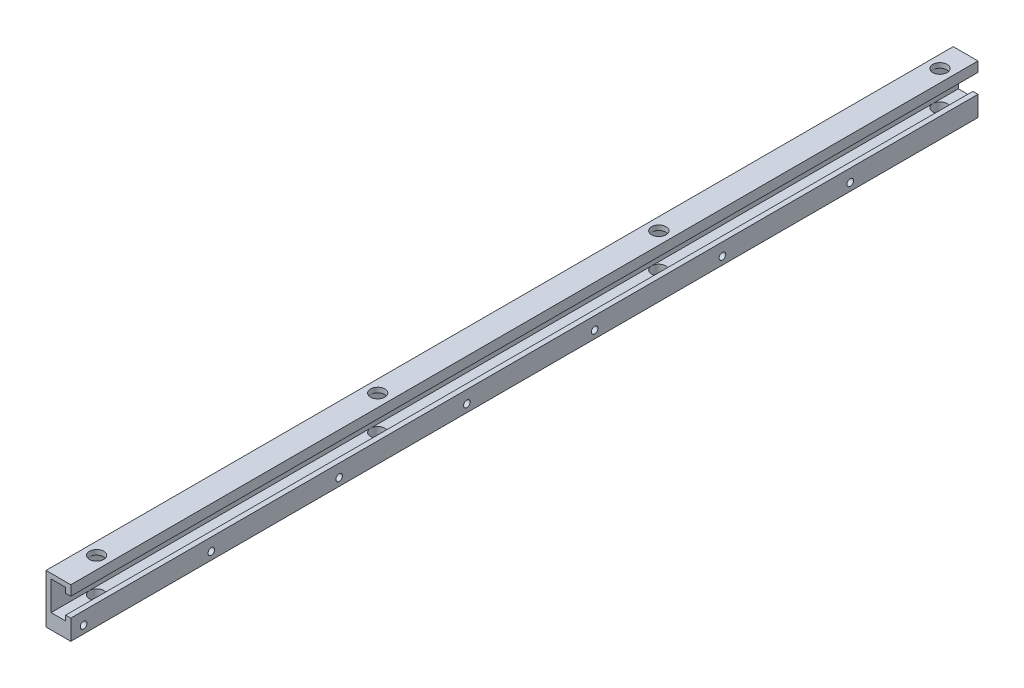
SolidWorks part; units mm, degrees
ref_plane "前视基准面" through (0, 0, 0) normal (0, 0, 1) x (1, 0, 0)
ref_plane "上视基准面" through (0, 0, 0) normal (0, 1, 0) x (1, 0, 0)
ref_plane "右视基准面" through (0, 0, 0) normal (1, 0, 0) x (0, 0, -1)
sketch "草图1" plane through (0, 0, 0) normal (0, 0, 1) x (1, 0, 0)
  line L0 (0, 0) -> (-3, 0) construction
  line L1 (-3, 0) -> (-3, 5.6)
  line L2 (-3, 0) -> (-3, -5.6)
  line L3 (6.7, -11.6) -> (-3, -11.6)
  line L4 (-3, 5.6) -> (-3, 7.6)
  line L5 (6.7, 7.6) -> (6.7, 3.7)
  line L6 (4.7, 5.7) -> (-1, 5.7)
  line L7 (-1, 0) -> (-1, -5.7)
  line L8 (6.7, 3.7) -> (4.7, 3.7)
  line L9 (4.7, 3.7) -> (4.7, 5.7)
  line L10 (-1, -5.7) -> (4.7, -5.7)
  line L11 (1.85, -5.7) -> (4.7, -5.7) construction
  line L12 (-3, 7.6) -> (2.6, 7.6)
  line L14 (-1, 5.7) -> (-1, 0)
  line L16 (4.7, -3.7) -> (4.7, -5.7)
  line L17 (4.7, -3.7) -> (6.7, -3.7)
  line L18 (6.7, -3.7) -> (6.7, -7.6)
  line L20 (2.6, 7.6) -> (6.7, 7.6)
  line L21 (-3, -5.6) -> (-3, -7.6)
  line L22 (-3, -7.6) -> (-3, -11.6)
  line L24 (6.7, -11.6) -> (6.7, -7.6)
extrude "凸台-拉伸1" add sketch "草图1" along normal blind 355
sketch "草图2" plane through (-3, 0, 0) normal (-1, 0, 0) x (0, 0, 1)
  line L0 (50, -8.6) -> (100, -8.6) construction
  line L1 (100, -8.6) -> (150, -8.6) construction
  line L2 (150, -8.6) -> (200, -8.6) construction
  line L3 (200, -8.6) -> (250, -8.6) construction
  line L4 (250, -8.6) -> (300, -8.6) construction
  line L5 (300, -8.6) -> (350, -8.6) construction
  circle A0 centre (200, -8.6) radius 2.8
  circle A1 centre (150, -8.6) radius 1.3
  circle A2 centre (100, -8.6) radius 1.3
  circle A3 centre (50, -8.6) radius 1.3
  circle A4 centre (250, -8.6) radius 2.8
  circle A5 centre (150, -8.6) radius 2.8
  circle A6 centre (100, -8.6) radius 2.8
  circle A7 centre (50, -8.6) radius 2.8
  circle A8 centre (300, -8.6) radius 2.8
  circle A9 centre (200, -8.6) radius 1.3
  circle A10 centre (250, -8.6) radius 1.3
  circle A11 centre (300, -8.6) radius 1.3
  circle A12 centre (350, -8.6) radius 1.3
  circle A13 centre (350, -8.6) radius 2.8
  point P9 (150, -8.6)
extrude "切除-拉伸1" cut sketch "草图2" against normal through all and the other way through all contours A3 | A2 | A2 | A1 | A1 | A9 | A10 | A11 | A12 region at (-3, -8.6, 150) region at (-3, -8.6, 100) region at (-3, -8.6, 50) region at (-3, -8.6, 200) region at (-3, -8.6, 250) region at (-3, -8.6, 300) region at (-3, -8.6, 350)
extrude "切除-拉伸2" cut sketch "草图2<3>" against normal blind 4 and the other way through all contours A7 A3 | A6 A2 | A6 A2 | A5 A1 | A5 A1 | A0 A9 | A4 A10 | A8 A11 | A13 A12 region at (-3, -8.6, 197.2792) region at (-3, -8.6, 247.2792) region at (-3, -8.6, 147.2792) region at (-3, -8.6, 97.2792) region at (-3, -8.6, 47.2792) region at (-3, -8.6, 297.2792) region at (-3, -8.6, 347.2792)
sketch "草图2<3>" plane through (-3, 0, 0) normal (-1, 0, 0) x (0, 0, 1) same geometry as "草图2"
sketch "草图13" plane through (0, 7.6, 0) normal (0, 1, 0) x (1, 0, 0)
  line L0 (-3, 0) -> (-3, -10)
  line L1 (-3, -355) -> (-3, 0) construction
  line L2 (-3, -10) -> (1.8, -10) construction
  line L3 (-3, -10) -> (-3, -120)
  line L4 (-3, -120) -> (1.8, -120) construction
  line L5 (-3, -355) -> (-3, -340)
  line L6 (-3, -340) -> (-3, -230)
  line L7 (-3, -340) -> (1.8, -340) construction
  line L8 (-3, -230) -> (1.8, -230) construction
  circle A0 centre (1.8, -10) radius 2.8
  circle A1 centre (1.8, -10) radius 1.6
  circle A2 centre (1.8, -120) radius 2.8
  circle A3 centre (1.8, -120) radius 1.6
  circle A4 centre (1.8, -340) radius 2.8
  circle A5 centre (1.8, -340) radius 1.6
  circle A6 centre (1.8, -230) radius 2.8
  circle A7 centre (1.8, -230) radius 1.6
extrude "切除-拉伸11" cut sketch "草图13" against normal blind 17 contours A0 A1 | A2 A3 | A6 A7 | A4 A5 region at (-0.9208, 7.6, 10) region at (-0.9208, 7.6, 120) region at (-0.9208, 7.6, 340) region at (-0.9208, 7.6, 230)
extrude "切除-拉伸12" cut sketch "草图13<4>" against normal through all contours A5 | A7 | A3 | A1 region at (1.8, 7.6, 10) region at (1.8, 7.6, 120) region at (1.8, 7.6, 340) region at (1.8, 7.6, 230)
sketch "草图13<4>" plane through (0, 7.6, 0) normal (0, 1, 0) x (1, 0, 0) same geometry as "草图13"
